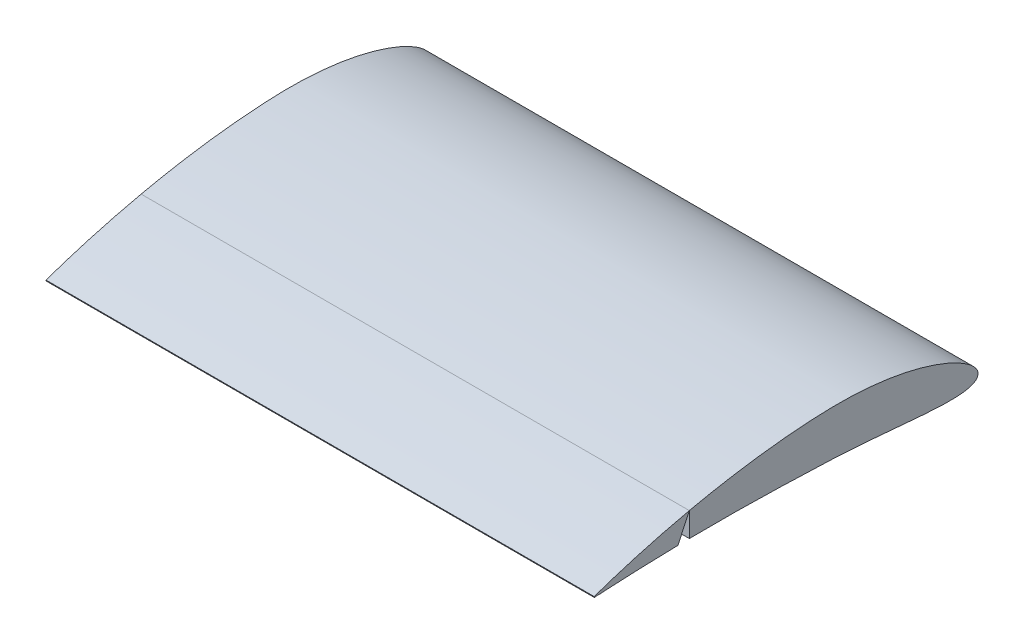
SolidWorks part; units mm, degrees
material "Thornel Mat VMA Foam Core"
ref_plane "Front Plane" through (0, 0, 0) normal (0, 0, 1) x (1, 0, 0)
ref_plane "Top Plane" through (0, 0, 0) normal (0, 1, 0) x (1, 0, 0)
ref_plane "Right Plane" through (0, 0, 0) normal (1, 0, 0) x (0, 0, -1)
curve "Curve1"
  spline degree 3 poles (0, 0.0012, 1.0003) (0, 0.0015, 0.9994) (0, 0.0028, 0.9958) (0, 0.0055, 0.9879) (0, 0.0099, 0.9747) (0, 0.0159, 0.9565) (0, 0.0233, 0.9333) (0, 0.0318, 0.9054) (0, 0.0411, 0.8731) (0, 0.051, 0.8366) (0, 0.0612, 0.7964) (0, 0.0713, 0.7528) (0, 0.0811, 0.7063) (0, 0.0903, 0.6574) (0, 0.0985, 0.6067) (0, 0.1057, 0.5546) (0, 0.1115, 0.5018) (0, 0.1158, 0.4488) (0, 0.1186, 0.3959) (0, 0.1189, 0.3436) (0, 0.1164, 0.2927) (0, 0.1112, 0.2442) (0, 0.1037, 0.1988) (0, 0.0942, 0.157) (0, 0.0831, 0.1194) (0, 0.0711, 0.0865) (0, 0.0584, 0.0585) (0, 0.0457, 0.0357) (0, 0.0334, 0.0184) (0, 0.0218, 0.0064) (0, 0.0108, -0.0005) (0, -0.0003, -0.0011) (0, -0.0092, 0.0055) (0, -0.0148, 0.017) (0, -0.0185, 0.0329) (0, -0.0204, 0.0533) (0, -0.0208, 0.0781) (0, -0.0198, 0.107) (0, -0.0176, 0.1398) (0, -0.0147, 0.176) (0, -0.0111, 0.2153) (0, -0.0074, 0.2574) (0, -0.0037, 0.3019) (0, -0.0005, 0.3484) (0, 0.002, 0.397) (0, 0.0037, 0.4471) (0, 0.0055, 0.4983) (0, 0.0069, 0.5496) (0, 0.0079, 0.6006) (0, 0.0085, 0.6505) (0, 0.0086, 0.699) (0, 0.0083, 0.7455) (0, 0.0076, 0.7894) (0, 0.0065, 0.8302) (0, 0.0053, 0.8675) (0, 0.0039, 0.9007) (0, 0.0027, 0.9296) (0, 0.0013, 0.9539) (0, 0.0006, 0.9727) (0, -0.0011, 0.9872) (0, 0, 0.9944) (0, -0.002, 0.9999) (0, -0.0005, 1) (0, 0, 1) knots 0 0 0 0 0.001372 0.005465 0.012235 0.021602 0.033461 0.047671 0.064081 0.082496 0.102719 0.124527 0.147676 0.171913 0.196978 0.222597 0.248497 0.274385 0.300041 0.32569 0.350525 0.37428 0.396711 0.417577 0.436654 0.453744 0.46868 0.481329 0.491631 0.499616 0.505546 0.510185 0.514824 0.520702 0.528516 0.538466 0.550543 0.564643 0.580638 0.598345 0.617584 0.638174 0.659922 0.682632 0.706121 0.730727 0.7557 0.780732 0.805564 0.829932 0.85357 0.876213 0.89761 0.917519 0.935698 0.951943 0.966047 0.97784 0.987174 0.993932 0.998018 0.999386 1 1 1 1
sketch "Sketch1" plane through (0, 0, 0) normal (1, 0, 0) x (0, 0, -1)
  line L0 (-354.7873, -0.0303) -> (-354.8762, 0.4104)
  line L1 (-354.7873, -0.0303) -> (0.8093, 1.5275) construction
  line L2 (0.8093, 1.5275) -> (0.7921, 5.4415) construction
  spline S1 degree 3 poles (-354.8762, 0.4104) (-354.5599, 0.5194) (-353.2997, 0.9536) (-350.4787, 1.9271) (-345.801, 3.4978) (-336.0241, 6.7216) (-319.6545, 11.7989) (-300.5983, 17.1306) (-282.4229, 21.7243) (-261.1758, 26.6516) (-238.6223, 31.1455) (-208.7748, 36.0048) (-183.9617, 39.0905) (-158.9023, 41.1132) (-140.0967, 42.1114) (-121.5167, 42.2289) (-103.4222, 41.3211) (-86.1884, 39.4787) (-70.0435, 36.8105) (-55.1998, 33.4329) (-41.8434, 29.5109) (-30.1305, 25.2201) (-20.187, 20.7343) (-12.1072, 16.2263) (-5.9269, 11.8553) (-1.6792, 7.7165) (0.7658, 3.7968) (0.9875, -0.1483) (-1.3511, -3.3089) (-5.4508, -5.2881) (-11.0873, -6.5875) (-18.3491, -7.2685) (-27.1638, -7.4049) (-37.4471, -7.0538) (-49.0831, -6.3019) (-61.9524, -5.238) (-75.9299, -3.9839) (-96.4067, -2.1536) (-117.9372, -0.4584) (-140.4848, 0.6745) (-158.2965, 1.2867) (-176.4839, 1.9179) (-200.672, 2.5862) (-224.5411, 2.9791) (-247.8302, 3.0285) (-264.3373, 2.9074) (-279.9331, 2.6564) (-294.438, 2.2829) (-307.6819, 1.8521) (-319.5134, 1.3711) (-329.7674, 0.9129) (-338.3889, 0.4268) (-345.077, 0.1915) (-350.2276, -0.4064) (-352.7802, -0.0354) (-354.7446, -0.7581) (-354.7772, -0.2025) (-354.7873, -0.0303) knots 0 0 0 0 0.001372 0.005465 0.012235 0.021602 0.047671 0.082496 0.102719 0.124527 0.171913 0.196978 0.248497 0.274385 0.300041 0.32569 0.350525 0.37428 0.396711 0.417577 0.436654 0.453744 0.46868 0.481329 0.491631 0.499616 0.505546 0.510185 0.514824 0.520702 0.528516 0.538466 0.550543 0.564643 0.580638 0.598345 0.617584 0.638174 0.682632 0.706121 0.730727 0.7557 0.780732 0.829932 0.85357 0.876213 0.89761 0.917519 0.935698 0.951943 0.966047 0.97784 0.987174 0.993932 0.998018 0.999386 1 1 1 1
  dimension "D1" = 355.6
extrude "Boss-Extrude1" add sketch "Sketch1" along normal blind 254 and the other way blind 254
sketch "Sketch2" plane through (-254, 0, 0) normal (-1, 0, 0) x (0, 0, 1)
  line L0 (266.7, 0) -> (266.7, 78.4574) construction
  line L1 (195.725, 0) -> (-195.725, 0) construction
  line L2 (0, -27.2986) -> (0, 27.2986) construction
  line L3 (266.7, 25.311) -> (266.7, 2.0657)
  line L4 (266.7, 25.311) -> (277.5394, 2.0657)
  line L5 (277.5394, 2.0657) -> (266.7, 2.0657)
  spline S0 degree 3 poles (354.7873, -0.0303) (354.7772, -0.2025) (354.7446, -0.7581) (352.7802, -0.0354) (350.2276, -0.4064) (345.077, 0.1915) (338.3889, 0.4268) (329.7674, 0.9129) (319.5134, 1.3711) (307.6819, 1.8521) (294.438, 2.2829) (279.9331, 2.6564) (264.3373, 2.9074) (247.8302, 3.0285) (224.5411, 2.9791) (200.672, 2.5862) (176.4839, 1.9179) (158.2965, 1.2867) (140.4848, 0.6745) (117.9372, -0.4584) (96.4067, -2.1536) (75.9299, -3.9839) (61.9524, -5.238) (49.0831, -6.3019) (37.4471, -7.0538) (27.1638, -7.4049) (18.3491, -7.2685) (11.0873, -6.5875) (5.4508, -5.2881) (1.3511, -3.3089) (-0.9875, -0.1483) (-0.7658, 3.7968) (1.6792, 7.7165) (5.9269, 11.8553) (12.1072, 16.2263) (20.187, 20.7343) (30.1305, 25.2201) (41.8434, 29.5109) (55.1998, 33.4329) (70.0435, 36.8105) (86.1884, 39.4787) (103.4222, 41.3211) (121.5167, 42.2289) (140.0967, 42.1114) (158.9023, 41.1132) (183.9617, 39.0905) (208.7748, 36.0048) (238.6223, 31.1455) (261.1758, 26.6516) (282.4229, 21.7243) (300.5983, 17.1306) (319.6545, 11.7989) (336.0241, 6.7216) (345.801, 3.4978) (350.4787, 1.9271) (353.2997, 0.9536) (354.5599, 0.5194) (354.8762, 0.4104) knots 0 0 0 0 0.000614 0.001982 0.006068 0.012826 0.02216 0.033953 0.048057 0.064302 0.082481 0.10239 0.123787 0.14643 0.170068 0.219268 0.2443 0.269273 0.293879 0.317368 0.361826 0.382416 0.401655 0.419362 0.435357 0.449457 0.461534 0.471484 0.479298 0.485176 0.489815 0.494454 0.500384 0.508369 0.518671 0.53132 0.546256 0.563346 0.582423 0.603289 0.62572 0.649475 0.67431 0.699959 0.725615 0.751503 0.803022 0.828087 0.875473 0.897281 0.917504 0.952329 0.978398 0.987765 0.994535 0.998628 1 1 1 1 construction
  dimension "D1" = 266.7
  dimension "D2" = 25
extrude "Cut-Extrude1" cut sketch "Sketch2" against normal up to next
